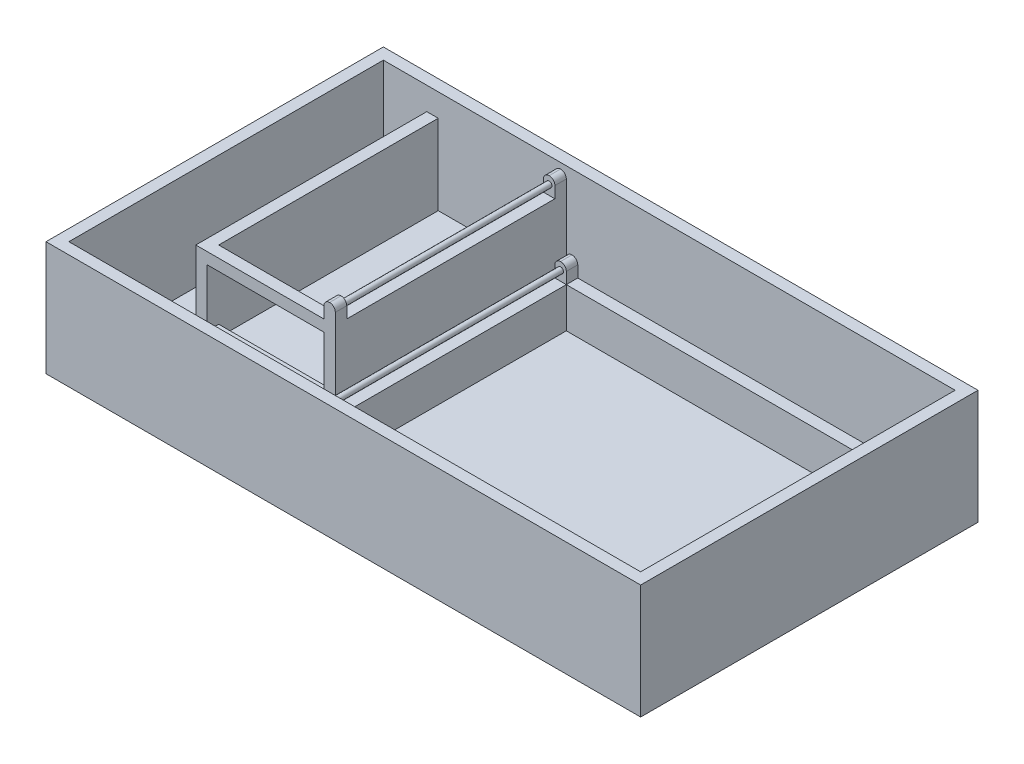
SolidWorks part; units mm, degrees
ref_plane "Front Plane" through (0, 0, 0) normal (0, 0, 1) x (1, 0, 0)
ref_plane "Top Plane" through (0, 0, 0) normal (0, 1, 0) x (1, 0, 0)
ref_plane "Right Plane" through (0, 0, 0) normal (1, 0, 0) x (0, 0, -1)
sketch "Sketch1" plane through (0, 0, 0) normal (0, 1, 0) x (1, 0, 0)
  line L1 (-63.5, 34.925) -> (63.5, 34.925)
  line L2 (-63.5, 34.925) -> (-63.5, -34.925)
  line L3 (-63.5, -34.925) -> (63.5, -34.925)
  line L4 (63.5, 34.925) -> (63.5, -34.925)
  line L5 (-63.5, 34.925) -> (63.5, -34.925) construction
  line L6 (-63.5, -34.925) -> (63.5, 34.925) construction
  line L7 (-66.04, 37.465) -> (66.04, 37.465)
  line L8 (-66.04, 37.465) -> (-66.04, -37.465)
  line L9 (-66.04, -37.465) -> (66.04, -37.465)
  line L10 (66.04, 37.465) -> (66.04, -37.465)
  line L11 (-66.04, 37.465) -> (66.04, -37.465) construction
  line L12 (-66.04, -37.465) -> (66.04, 37.465) construction
  point P0 (0, 0)
  point P6 (0, 0)
  dimension "D1" = 127
  dimension "D2" = 69.85
  dimension "D3" = 132.08
  dimension "D4" = 74.93
extrude "Base" add sketch "Sketch1" along normal blind 2.54 contours L2 L3 L4 L1
sketch "Sketch2" plane through (0, 2.54, 0) normal (0, 1, 0) x (1, 0, 0)
  line L0 (-63.5, 34.925) -> (63.5, 34.925) construction
  line L1 (-13.97, 26.035) -> (54.61, 26.035)
  line L2 (-13.97, 26.035) -> (-13.97, -27.305)
  line L3 (-13.97, -27.305) -> (54.61, -27.305)
  line L4 (54.61, 26.035) -> (54.61, -27.305)
  line L5 (-13.97, 26.035) -> (54.61, -27.305) construction
  line L6 (-13.97, -27.305) -> (54.61, 26.035) construction
  line L7 (63.5, 34.925) -> (63.5, -34.925) construction
  line L9 (-16.51, -29.845) -> (57.15, -29.845)
  line L10 (-16.51, -29.845) -> (-16.51, 28.575)
  line L11 (-16.51, 28.575) -> (57.15, 28.575)
  line L12 (57.15, -29.845) -> (57.15, 28.575)
  line L13 (-16.51, -29.845) -> (57.15, 28.575) construction
  line L14 (-16.51, 28.575) -> (57.15, -29.845) construction
  point P0 (20.32, -0.635)
  point P9 (20.32, -0.635)
  dimension "D1" = 8.89
  dimension "D2" = 8.89
  dimension "D3" = 53.34
  dimension "D4" = 68.58
  dimension "D5" = 73.66
  dimension "D6" = 58.42
extrude "PCB-Holder" add sketch "Sketch2" along normal blind 8.89 contours L1 L4 L3 L2 | L11 L12 L9 L10
sketch "Sketch4" plane through (-16.51, 0, 0) normal (-1, 0, 0) x (0, 0, 1)
  line L0 (-28.575, 11.43) -> (-28.575, 2.54) construction
  line L1 (29.845, 11.43) -> (-28.575, 11.43) construction
  circle A0 centre (22.225, 6.985) radius 1.5875
  dimension "D1" = 50.8
  dimension "D2" = 3.175
  dimension "D3" = 4.445
extrude "Boss-Extrude5" add sketch "Sketch1<3>" along normal blind 25.4
sketch "Sketch1<3>" plane through (0, 0, 0) normal (0, 1, 0) x (1, 0, 0) same geometry as "Sketch1"
sketch "Sketch6" plane through (0, 2.54, 0) normal (0, 1, 0) x (1, 0, 0)
  line L0 (-63.5, 34.925) -> (63.5, 34.925) construction
  line L1 (-51.308, 34.925) -> (-25.4, 34.925)
  line L2 (-51.308, 34.925) -> (-51.308, -13.843)
  line L3 (-51.308, -13.843) -> (-25.4, -13.843)
  line L4 (-25.4, 34.925) -> (-25.4, -13.843)
  line L5 (-16.51, -29.845) -> (-16.51, 28.575) construction
  line L6 (-53.848, 34.925) -> (-53.848, -16.383)
  line L7 (-53.848, 34.925) -> (-22.86, 34.925)
  line L8 (-53.848, -16.383) -> (-22.86, -16.383)
  line L9 (-22.86, 34.925) -> (-22.86, -16.383)
  line M9 (63.5, 34.925) -> (-63.5, 34.925)
  dimension "D1" = 8.89
  dimension "D2" = 25.908
  dimension "D3" = 48.768
  dimension "D4" = 2.54
  dimension "D5" = 2.54
  dimension "D6" = 2.54
extrude "Boss-Extrude6" add sketch "Sketch6" along normal blind 17.78 contours L9 L4 L3 L2 L6 L8 M9 region at (-51.9074, 2.54, -10.541)
sketch "Sketch7" plane through (0, 0, 16.383) normal (0, 0, 1) x (1, 0, 0)
  line L0 (-53.848, 20.32) -> (-22.86, 20.32) construction
  line L1 (-51.308, 17.78) -> (-25.4, 17.78)
  line L2 (-51.308, 17.78) -> (-51.308, 5.08)
  line L3 (-51.308, 5.08) -> (-25.4, 5.08)
  line L4 (-25.4, 17.78) -> (-25.4, 5.08)
  line L5 (-51.308, 17.78) -> (-25.4, 5.08) construction
  line L6 (-51.308, 5.08) -> (-25.4, 17.78) construction
  line L7 (-22.86, 20.32) -> (-22.86, 2.54) construction
  line L8 (-53.848, 20.32) -> (-53.848, 2.54) construction
  line L9 (-53.848, 2.54) -> (-22.86, 2.54) construction
  point P0 (-38.354, 11.43)
  dimension "D1" = 2.54
  dimension "D2" = 2.54
  dimension "D3" = 2.54
  dimension "D4" = 2.54
extrude "Battery-Gap" cut sketch "Sketch7" against normal up to vertex (2.54 mm away) up to point (-25.4, 20.32, 13.843)
extrude "Wire-Gap" cut sketch "Sketch4" against normal blind 2.54
sketch "Sketch8" plane through (0, 11.43, 0) normal (0, 1, 0) x (1, 0, 0)
  line L0 (-13.97, 26.035) -> (-13.97, -27.305) construction
  line L1 (-16.51, 28.575) -> (-13.97, 28.575)
  line L2 (-16.51, 28.575) -> (-16.51, -29.845)
  line L3 (-16.51, -29.845) -> (-13.97, -29.845)
  line L4 (-13.97, 28.575) -> (-13.97, -29.845)
  line L5 (-16.51, -29.845) -> (-16.51, 28.575) construction
  line L6 (-16.51, 28.575) -> (57.15, 28.575) construction
  line L7 (-16.51, -29.845) -> (57.15, -29.845) construction
  line L9 (-16.51, -29.845) -> (-13.97, -29.845)
  line L10 (-16.51, -29.845) -> (-16.51, -27.305)
  line L11 (-16.51, -27.305) -> (-13.97, -27.305)
  line L12 (-13.97, -29.845) -> (-13.97, -27.305)
  line L13 (-16.51, 28.575) -> (-13.97, 28.575)
  line L14 (-16.51, 28.575) -> (-16.51, 26.035)
  line L15 (-16.51, 26.035) -> (-13.97, 26.035)
  line L16 (-13.97, 28.575) -> (-13.97, 26.035)
  line M5 (-16.51, 28.575) -> (-16.51, -29.845)
  line M6 (-16.51, -29.845) -> (57.15, -29.845)
  line M8 (57.15, 28.575) -> (-16.51, 28.575)
extrude "PCB-Holder-Hinge" add sketch "Sketch8" along normal blind 3.81 contours L11 L2 L4 M6 | L15 L4 M5 M8 region at (-15.24, 11.43, -27.305) region at (-15.24, 11.43, 28.575)
fillet "Fillet4" radius 1.27 4 edges at (-16.51, 15.24, -27.305) (-13.97, 15.24, -27.305) (-13.97, 15.24, 28.575) (-16.51, 15.24, 28.575)
sketch "Sketch13" plane through (0, 0, -26.035) normal (0, 0, 1) x (1, 0, 0)
  line L0 (-13.97, 13.97) -> (-13.97, 11.43) construction
  line L2 (-16.51, 11.43) -> (-13.97, 11.43) construction
  circle A0 centre (-15.24, 13.589) radius 0.635
  dimension "D1" = 1.27
  dimension "D2" = 2.159
  dimension "D3" = 1.27
extrude "Boss-Extrude10" add sketch "Sketch13" along normal up to vertex (53.34 mm away) up to point (-13.97, 13.97, 27.305)
sketch "Sketch14" plane through (0, 20.32, 0) normal (0, 1, 0) x (1, 0, 0)
  line L0 (-22.86, 34.925) -> (-22.86, -16.383) construction
  line L1 (-22.86, -16.383) -> (-25.4, -16.383)
  line L2 (-22.86, -16.383) -> (-22.86, -13.843)
  line L3 (-22.86, -13.843) -> (-25.4, -13.843)
  line L4 (-25.4, -16.383) -> (-25.4, -13.843)
  line L5 (-25.4, 34.925) -> (-22.86, 34.925)
  line L6 (-25.4, 34.925) -> (-25.4, 32.385)
  line L7 (-25.4, 32.385) -> (-22.86, 32.385)
  line L8 (-22.86, 34.925) -> (-22.86, 32.385)
  dimension "D1" = 2.54
extrude "Boss-Extrude11" add sketch "Sketch14" along normal blind 3.81
fillet "Fillet5" radius 1.27 4 edges at (-22.86, 24.13, -33.655) (-25.4, 24.13, -33.655) (-25.4, 24.13, 15.113) (-22.86, 24.13, 15.113)
sketch "Sketch15" plane through (0, 0, -32.385) normal (0, 0, 1) x (1, 0, 0)
  line L0 (-25.4, 20.32) -> (-22.86, 20.32) construction
  line L1 (-22.86, 22.86) -> (-22.86, 20.32) construction
  circle A0 centre (-24.13, 22.479) radius 0.635
  dimension "D2" = 1.27
  dimension "D3" = 1.27
  dimension "D1" = 2.159
extrude "Boss-Extrude13" add sketch "Sketch15" along normal up to vertex (46.228 mm away) contours A0 up to point (-22.86, 22.86, 13.843)
